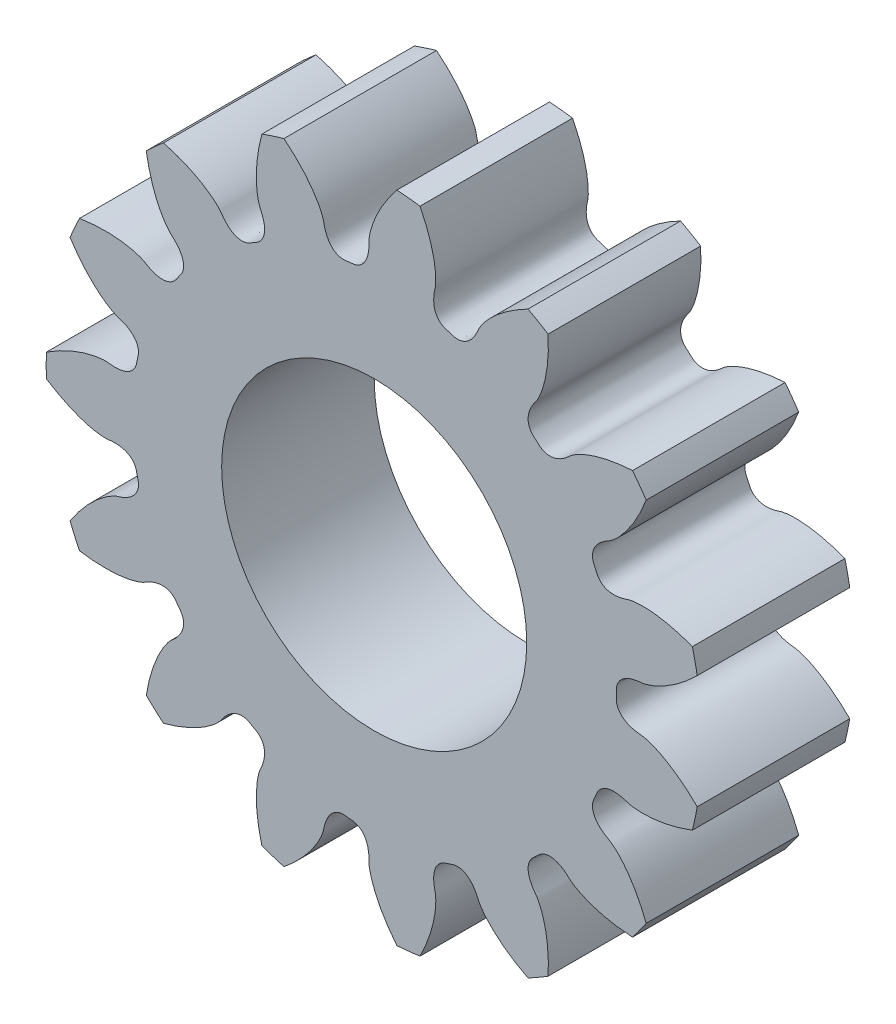
SolidWorks part; units mm, degrees
ref_plane "Front Plane" through (0, 0, 0) normal (0, 0, 1) x (1, 0, 0)
ref_plane "Top Plane" through (0, 0, 0) normal (0, 1, 0) x (1, 0, 0)
ref_plane "Right Plane" through (0, 0, 0) normal (1, 0, 0) x (0, 0, -1)
ref_axis "Axis1" through (0, 0, 55) along (0, 0, -1)
sketch "SketchRevolveSpurPinion" plane through (0, 0, 0) normal (1, 0, 0) x (0, 0, -1)
  line L0 (0, 0) -> (1, 0) construction
  line L1 (-2, 0) -> (-2, 8.6)
  line L2 (-2, 8.6) -> (2, 8.6)
  line L3 (2, 8.6) -> (2, 0)
  line L4 (2, 0) -> (-2, 0)
  dimension "Side1" = 2
  dimension "OutsideRadius" = 8.6
  dimension "Side2" = 2
revolve "SpurPinion" add sketch "SketchRevolveSpurPinion" angle 360 about L0
sketch "SketchToothSpurPinion" plane through (0, 0, 0) normal (0, 0, 1) x (1, 0, 0)
  arc A0 (8.5175, 1.5368) -> (8.5175, -1.5368) centre (0, 0) cw
  spline S0 degree 3 poles (8.5175, -1.5368) (8.4383, -1.4556) (8.3186, -1.341) (8.1555, -1.201) (8.04, -1.1088) (7.9286, -1.0262) (7.8216, -0.9526) (7.7196, -0.8877) (7.6231, -0.831) (7.5325, -0.782) (7.4483, -0.7403) (7.3707, -0.7053) (7.3003, -0.6764) (7.2373, -0.6532) (7.182, -0.635) (7.1347, -0.6212) (7.0957, -0.6114) (7.065, -0.6048) (6.9983, -0.5928) (6.9243, -0.5911) (6.8439, -0.5764) (6.7977, -0.5664) (6.7531, -0.5544) (6.7099, -0.5405) (6.6681, -0.5245) (6.6275, -0.5062) (6.5881, -0.4853) (6.5498, -0.4613) (6.5127, -0.4337) (6.4768, -0.4017) (6.4427, -0.3644) (6.4113, -0.3211) (6.3842, -0.271) (6.3632, -0.2143) (6.3519, -0.1569) (6.3475, -0.0849) (6.3517, 0) (6.3475, 0.0849) (6.3519, 0.1569) (6.3632, 0.2143) (6.3842, 0.271) (6.4113, 0.3211) (6.4427, 0.3644) (6.4768, 0.4017) (6.5127, 0.4337) (6.5498, 0.4613) (6.5881, 0.4853) (6.6275, 0.5062) (6.6681, 0.5245) (6.7099, 0.5405) (6.7531, 0.5544) (6.7977, 0.5664) (6.8439, 0.5764) (6.9243, 0.5911) (6.9983, 0.5928) (7.065, 0.6048) (7.0957, 0.6114) (7.1347, 0.6212) (7.182, 0.635) (7.2373, 0.6532) (7.3003, 0.6764) (7.3707, 0.7053) (7.4483, 0.7403) (7.5325, 0.782) (7.6231, 0.831) (7.7196, 0.8877) (7.8216, 0.9526) (7.9286, 1.0262) (8.04, 1.1088) (8.1555, 1.201) (8.3186, 1.341) (8.4383, 1.4556) (8.5175, 1.5368) knots 0 0 0 0 0.060357 0.088153 0.114361 0.138981 0.162012 0.183455 0.203309 0.221575 0.238253 0.253342 0.266843 0.278756 0.28908 0.297816 0.304963 0.310523 0.314494 0.341047 0.349641 0.358013 0.366194 0.374221 0.38214 0.390006 0.397886 0.405863 0.414034 0.422511 0.431414 0.440858 0.45093 0.461643 0.472911 0.481918 0.5 0.518082 0.527089 0.538357 0.54907 0.559142 0.568586 0.577489 0.585966 0.594137 0.602114 0.609994 0.61786 0.625779 0.633806 0.641987 0.650359 0.658953 0.685506 0.689477 0.695037 0.702184 0.71092 0.721244 0.733157 0.746658 0.761747 0.778425 0.796691 0.816545 0.837988 0.861019 0.885639 0.911847 0.939643 1 1 1 1
extrude "ToothExtrudeCutSpurPinion" cut sketch "SketchToothSpurPinion" against normal blind 2 and the other way blind 2
pattern_circular "PatternSpurPinion" count 15 every 24 about axis through (0, 0, 55) along (0, 0, -1) of "ToothExtrudeCutSpurPinion"
sketch "BoreRevolveSketch" plane through (0, 0, 0) normal (1, 0, 0) x (0, 0, -1)
  line L0 (0, 0) -> (1, 0) construction
  line L1 (-2, 0) -> (2, 0)
  line L2 (2, 0) -> (2, 4)
  line L3 (2, 4) -> (-2, 4)
  line L4 (-2, 4) -> (-2, 0)
  dimension "BoreSide1" = 2
  dimension "TaperSide1" = 4
  dimension "BoreSide2" = 2
  dimension "TaperSide2" = 4
revolve "BoreRevolveCut" cut sketch "BoreRevolveSketch" angle 360 about L0
sketch "AuxiliarySketchSpurPinion" plane through (0, 0, 0) normal (0, 0, 1) x (1, 0, 0)
  circle A0 centre (0, 0) radius 7.5 construction
  circle A1 centre (0, 0) radius 7.0477 construction
  circle A2 centre (0, 0) radius 7.0511 construction
  circle A3 centre (0, 0) radius 8.6 construction
  circle A4 centre (0, 0) radius 6.35 construction
  dimension "PitchDiameter" = 15
  dimension "BaseDiameter" = 14.0954
  dimension "FormDiameter" = 14.1023
  dimension "MajorDiameter" = 17.2
  dimension "MinorDiameter" = 12.7
